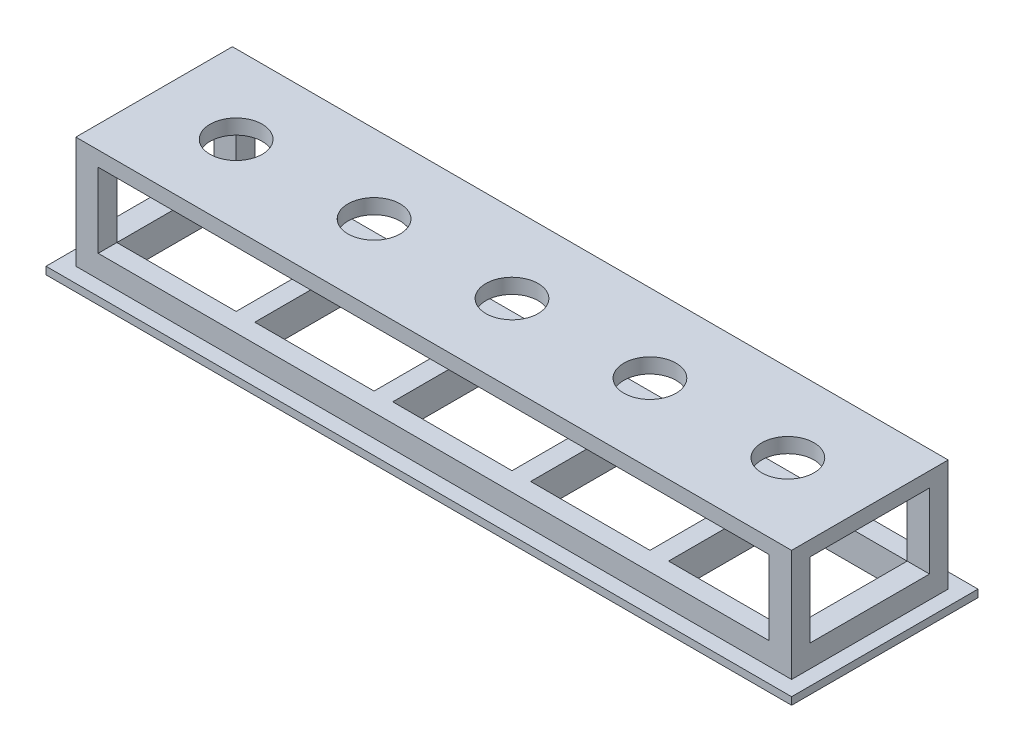
SolidWorks part; units mm, degrees
ref_plane "Front Plane" through (0, 0, 0) normal (0, 0, 1) x (1, 0, 0)
ref_plane "Top Plane" through (0, 0, 0) normal (0, 1, 0) x (1, 0, 0)
ref_plane "Right Plane" through (0, 0, 0) normal (1, 0, 0) x (0, 0, -1)
sketch "Sketch1" plane through (0, 0, 0) normal (0, 1, 0) x (1, 0, 0)
  line L1 (-48, 10.5) -> (48, 10.5)
  line L2 (-48, 10.5) -> (-48, -10.5)
  line L3 (-48, -10.5) -> (48, -10.5)
  line L4 (48, 10.5) -> (48, -10.5)
  line L5 (-48, 10.5) -> (48, -10.5) construction
  line L6 (-48, -10.5) -> (48, 10.5) construction
  point P0 (0, 0)
extrude "Boss-Extrude1" add sketch "Sketch1" along normal blind 3
sketch "Sketch2" plane through (0, 3, 0) normal (0, 1, 0) x (1, 0, 0)
  line L3 (-8, 8) -> (8, 8)
  line L4 (-8, 8) -> (-8, -8)
  line L5 (-45, 8) -> (-29, 8)
  line L6 (-45, 8) -> (-45, -8)
  line L7 (-45, -8) -> (-29, -8)
  line L8 (-29, 8) -> (-29, -8)
  line L9 (-45, 8) -> (-29, -8) construction
  line L10 (-45, -8) -> (-29, 8) construction
  line L11 (-26.5, 8) -> (-10.5, 8)
  line L12 (-26.5, 8) -> (-26.5, -8)
  line L13 (-26.5, -8) -> (-10.5, -8)
  line L14 (-10.5, 8) -> (-10.5, -8)
  line L15 (-26.5, 8) -> (-10.5, -8) construction
  line L16 (-26.5, -8) -> (-10.5, 8) construction
  line L17 (-8, -8) -> (8, -8)
  line L20 (8, 8) -> (8, -8)
  line L21 (-8, 8) -> (8, -8) construction
  line L22 (-8, -8) -> (8, 8) construction
  line L32 (10.5, 8) -> (26.5, 8)
  line L33 (10.5, 8) -> (10.5, -8)
  line L34 (10.5, -8) -> (26.5, -8)
  line L35 (26.5, 8) -> (26.5, -8)
  line L36 (10.5, 8) -> (26.5, -8) construction
  line L37 (10.5, -8) -> (26.5, 8) construction
  line L39 (29, 8) -> (45, 8)
  line L40 (29, 8) -> (29, -8)
  line L41 (29, -8) -> (45, -8)
  line L42 (45, 8) -> (45, -8)
  line L43 (29, 8) -> (45, -8) construction
  line L44 (29, -8) -> (45, 8) construction
  dimension "D1" = 16
  dimension "D2" = 16
  dimension "D3" = 16
  dimension "D4" = 16
  dimension "D5" = 16
  dimension "D6" = 16
  dimension "D7" = 16
  dimension "D8" = 16
  dimension "D9" = 16
  dimension "D10" = 16
extrude "Cut-Extrude3" cut sketch "Sketch2" against normal blind 7 and the other way blind 7
sketch "Sketch5" plane through (0, 3, 0) normal (0, 1, 0) x (1, 0, 0)
  line L0 (-45, 8) -> (-45, 10.5)
  line L1 (48, 10.5) -> (-48, 10.5) construction
  line L2 (-45, -8) -> (-45, -10.5)
  line L4 (-48, -10.5) -> (48, -10.5) construction
  line L5 (-48, 10.5) -> (-45, 10.5)
  line L6 (-48, 10.5) -> (-48, 8)
  line L7 (-48, 8) -> (-45, 8)
  line L8 (-45, 10.5) -> (-45, 8)
  line L9 (-48, 10.5) -> (-45, 8) construction
  line L10 (-48, 8) -> (-45, 10.5) construction
  line L11 (45, 8) -> (45, 10.5)
  line L12 (-48, 10.5) -> (-48, -10.5) construction
  line L13 (45, -8) -> (48, -8)
  line L14 (-48, -8) -> (-45, -8)
  line L15 (-48, -8) -> (-48, -10.5)
  line L16 (-48, -10.5) -> (-45, -10.5)
  line L17 (-45, -8) -> (-45, -10.5)
  line L18 (-48, -8) -> (-45, -10.5) construction
  line L19 (-48, -10.5) -> (-45, -8) construction
  line L20 (48, -10.5) -> (48, 10.5) construction
  line L22 (45, 10.5) -> (48, 10.5)
  line L23 (45, 10.5) -> (45, 8)
  line L24 (45, 8) -> (48, 8)
  line L25 (48, 10.5) -> (48, 8)
  line L26 (45, 10.5) -> (48, 8) construction
  line L27 (45, 8) -> (48, 10.5) construction
  line L29 (45, -8) -> (48, -8)
  line L30 (45, -8) -> (45, -10.5)
  line L31 (45, -10.5) -> (48, -10.5)
  line L32 (48, -8) -> (48, -10.5)
  line L33 (45, -8) -> (48, -10.5) construction
  line L34 (45, -10.5) -> (48, -8) construction
  point P9 (-46.5, 9.25)
  point P10 (-46.5, -9.25)
  point P21 (46.5, 9.25)
  point P29 (46.5, -9.25)
  line M37 (48, -10.5) -> (48, 10.5)
  line M38 (48, 10.5) -> (-48, 10.5)
  line M39 (-48, 10.5) -> (-48, -10.5)
  line M40 (-48, -10.5) -> (48, -10.5)
extrude "Boss-Extrude5" add sketch "Sketch5" along normal blind 10 contours L7 L0 M39 M38 | L14 L2 M39 M40 | L11 L24 M37 M38 | L13 L30 M40 M37 region at (-46.5, 3, -9.25) region at (46.5, 3, -9.25) region at (-46.5, 3, 9.25) region at (46.5, 3, 9.25)
sketch "Sketch6" plane through (0, 13, 0) normal (0, 1, 0) x (1, 0, 0)
  line L1 (-48, 10.5) -> (48, 10.5)
  line L2 (-48, 10.5) -> (-48, -10.5)
  line L3 (-48, -10.5) -> (48, -10.5)
  line L4 (48, 10.5) -> (48, -10.5)
  line L5 (-48, 10.5) -> (48, -10.5) construction
  line L6 (-48, -10.5) -> (48, 10.5) construction
  point P0 (0, 0)
extrude "Boss-Extrude6" add sketch "Sketch6" along normal blind 2
sketch "Sketch7" plane through (0, 15, 0) normal (0, 1, 0) x (1, 0, 0)
  circle A0 centre (-37, 0) radius 3.5
  circle A1 centre (-18.5, 0) radius 3.5
  circle A2 centre (0, 0) radius 3.5
  circle A3 centre (18.5, 0) radius 3.5
  circle A4 centre (37, 0) radius 3.5
extrude "Cut-Extrude5" cut sketch "Sketch7" against normal blind 2
sketch "Sketch9" plane through (0, 0, 0) normal (0, -1, 0) x (1, 0, 0)
  line L1 (-50, 12.5) -> (50, 12.5)
  line L2 (-50, 12.5) -> (-50, -12.5)
  line L3 (-50, -12.5) -> (50, -12.5)
  line L4 (50, 12.5) -> (50, -12.5)
  line L5 (-50, 12.5) -> (50, -12.5) construction
  line L6 (-50, -12.5) -> (50, 12.5) construction
  point P0 (0, 0)
  dimension "D1" = 100
  dimension "D2" = 25
extrude "Boss-Extrude7" add sketch "Sketch9" along normal blind 1
sketch "Sketch10" plane through (0, -1, 0) normal (0, -1, 0) x (1, 0, 0)
  line L3 (-45, 8) -> (-29, 8)
  line L4 (-45, 8) -> (-45, -8)
  line L5 (-45, -8) -> (-29, -8)
  line L6 (-29, 8) -> (-29, -8)
  line L7 (-45, 8) -> (-29, -8) construction
  line L8 (-45, -8) -> (-29, 8) construction
  line L10 (-26.5, 8) -> (-10.5, 8)
  line L11 (-26.5, 8) -> (-26.5, -8)
  line L12 (-26.5, -8) -> (-10.5, -8)
  line L13 (-10.5, 8) -> (-10.5, -8)
  line L14 (-26.5, 8) -> (-10.5, -8) construction
  line L15 (-26.5, -8) -> (-10.5, 8) construction
  line L17 (-8, 8) -> (8, 8)
  line L18 (-8, 8) -> (-8, -8)
  line L19 (-8, -8) -> (8, -8)
  line L20 (8, 8) -> (8, -8)
  line L21 (-8, 8) -> (8, -8) construction
  line L22 (-8, -8) -> (8, 8) construction
  line L24 (10.5, 8) -> (26.5, 8)
  line L25 (10.5, 8) -> (10.5, -8)
  line L26 (10.5, -8) -> (26.5, -8)
  line L27 (26.5, 8) -> (26.5, -8)
  line L28 (10.5, 8) -> (26.5, -8) construction
  line L29 (10.5, -8) -> (26.5, 8) construction
  line L31 (29, 8) -> (45, 8)
  line L32 (29, 8) -> (29, -8)
  line L33 (29, -8) -> (45, -8)
  line L34 (45, 8) -> (45, -8)
  line L35 (29, 8) -> (45, -8) construction
  line L36 (29, -8) -> (45, 8) construction
  dimension "D1" = 16
  dimension "D2" = 16
  dimension "D3" = 16
  dimension "D4" = 16
  dimension "D5" = 16
  dimension "D6" = 16
  dimension "D7" = 16
  dimension "D8" = 16
  dimension "D9" = 16
  dimension "D10" = 16
extrude "Cut-Extrude6" cut sketch "Sketch10" against normal blind 1
